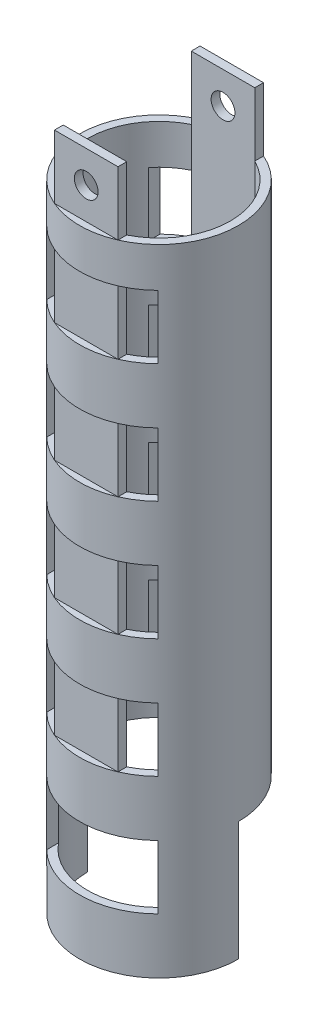
SolidWorks part; units mm, degrees
ref_plane "Front Plane" through (0, 0, 0) normal (0, 0, 1) x (1, 0, 0)
ref_plane "Top Plane" through (0, 0, 0) normal (0, 1, 0) x (1, 0, 0)
ref_plane "Right Plane" through (0, 0, 0) normal (1, 0, 0) x (0, 0, -1)
sketch "Sketch1" plane through (0, 0, 0) normal (0, 1, 0) x (1, 0, 0)
  circle A0 centre (0, 0) radius 50
  dimension "D1" = 100
extrude "Boss-Extrude1" add sketch "Sketch1" along normal blind 400
shell "Shell1" thickness 10 removed face at (0, 0, 50)
sketch "Sketch2" plane through (0, 390, 0) normal (0, -1, 0) x (1, 0, 0)
  circle A1 centre (0, 0) radius 40
  circle A2 centre (0, 0) radius 40
  dimension "D1" = 0
extrude "Cut-Extrude1" cut sketch "Sketch2" against normal blind 400
sketch "Sketch3" plane through (0, 0, 0) normal (0, 0, 1) x (1, 0, 0)
  line L0 (50, 400) -> (-50, 400) construction
  line L1 (-35, 375) -> (35, 375)
  line L2 (-35, 375) -> (-35, 335)
  line L3 (-35, 335) -> (35, 335)
  line L4 (35, 375) -> (35, 335)
  line L5 (-35, 300) -> (-35, 260)
  line L6 (-35, 300) -> (35, 300)
  line L7 (35, 300) -> (35, 260)
  line L8 (-35, 260) -> (35, 260)
  line L9 (-35, 225) -> (-35, 185)
  line L10 (-35, 225) -> (35, 225)
  line L11 (35, 225) -> (35, 185)
  line L12 (-35, 185) -> (35, 185)
  line L13 (-35, 150) -> (-35, 110)
  line L14 (-35, 150) -> (35, 150)
  line L15 (35, 150) -> (35, 110)
  line L16 (-35, 110) -> (35, 110)
  line L17 (-35, 75) -> (-35, 35)
  line L18 (-35, 75) -> (35, 75)
  line L19 (35, 75) -> (35, 35)
  line L20 (-35, 35) -> (35, 35)
  point P4 (0, 335)
  dimension "D1" = 70
  dimension "D2" = 40
  dimension "D3" = 25
  dimension "D4" = 5
extrude "Cut-Extrude2" cut sketch "Sketch3" against normal mid plane 400 contours L2 L1 L4 L3 | L5 L8 L7 L6 | L9 L12 L11 L10 | L13 L16 L15 L14 | L17 L20 L19 L18
sketch "Sketch4" plane through (0, 400, 0) normal (0, 1, 0) x (1, 0, 0)
  circle A0 centre (0, 0) radius 45
extrude "Cut-Extrude3" cut sketch "Sketch4" against normal blind 400
sketch "Sketch5" plane through (0, 400, 0) normal (0, 1, 0) x (1, 0, 0)
  line L0 (0, 56.0301) -> (0, -62.1365) construction
  line L1 (-46.8375, 17.5) -> (-38.8375, 17.5)
  line L2 (-46.8375, 17.5) -> (-46.8375, -17.5)
  line L3 (-46.8375, -17.5) -> (-38.8375, -17.5)
  line L4 (-38.8375, 17.5) -> (-38.8375, -17.5)
  line L5 (46.8375, -17.5) -> (38.8375, -17.5)
  line L6 (38.8375, 17.5) -> (38.8375, -17.5)
  line L7 (46.8375, 17.5) -> (38.8375, 17.5)
  line L8 (46.8375, 17.5) -> (46.8375, -17.5)
  circle A0 centre (0, 0) radius 50 construction
  point P6 (-38.8375, 0)
  dimension "D1" = 35
  dimension "D2" = 8
sketch "Sketch8" plane through (0, 0, 0) normal (0, 1, 0) x (1, 0, 0)
  line L0 (-50, 0) -> (50, 0)
  circle A0 centre (0, 0) radius 50
extrude "Cut-Extrude7" cut sketch "Sketch8" along normal blind 75 contours L0 A0 region at (0, 0, -21.2207)
sketch "Sketch9" plane through (0, 400, 0) normal (0, 1, 0) x (1, 0, 0)
  line L0 (-79.4702, 0) -> (86.1334, 0) construction
  line L1 (20, 45.8258) -> (-20, 45.8258)
  line L2 (20, 45.8258) -> (20, 40.3113)
  line L3 (20, 40.3113) -> (-20, 40.3113)
  line L4 (-20, 45.8258) -> (-20, 40.3113)
  line L5 (20, -40.3113) -> (-20, -40.3113)
  line L6 (-20, -45.8258) -> (-20, -40.3113)
  line L7 (20, -45.8258) -> (-20, -45.8258)
  line L8 (20, -45.8258) -> (20, -40.3113)
  circle A0 centre (0, 0) radius 50 construction
  circle A1 centre (0, 0) radius 45 construction
  dimension "D1" = 40
extrude "Boss-Extrude3" add sketch "Sketch9" against normal up to surface (325 mm away) and the other way blind 40 up to face at (0, 75, -23.75)
sketch "Sketch10" plane through (0, 0, -45.8258) normal (0, 0, -1) x (-1, 0, 0)
  line L0 (-20, 440) -> (20, 440) construction
  line L3 (20, 440) -> (20, 400) construction
  circle A0 centre (0, 420) radius 7.5
  point P2 (0, 0)
  point P5 (20, 420)
  point P8 (0, 440)
  dimension "D1" = 15
extrude "Cut-Extrude8" cut sketch "Sketch10" against normal through all
